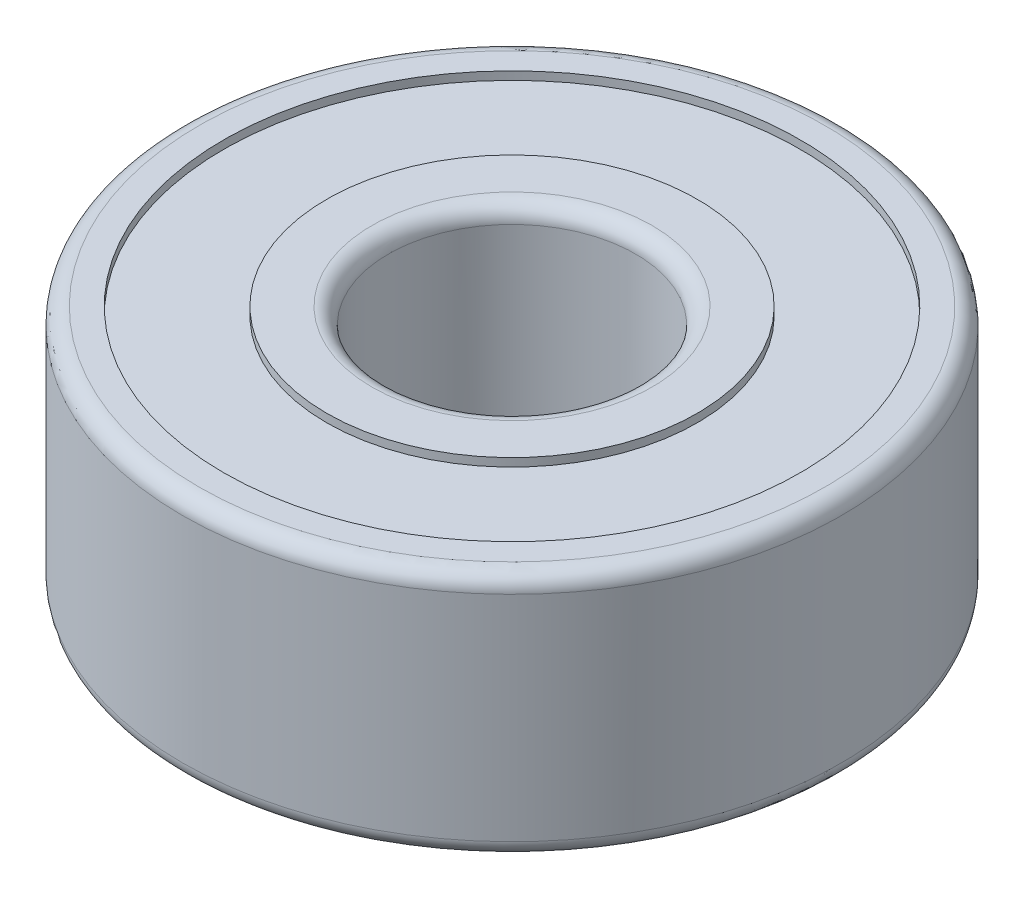
SolidWorks part; units mm, degrees
material "Plain Carbon Steel"
ref_plane "Front Plane" through (0, 0, 0) normal (0, 0, 1) x (1, 0, 0)
ref_plane "Top Plane" through (0, 0, 0) normal (0, 1, 0) x (1, 0, 0)
ref_plane "Right Plane" through (0, 0, 0) normal (1, 0, 0) x (0, 0, -1)
sketch "Sketch1" plane through (0, 0, 0) normal (1, 0, 0) x (0, 0, -1)
  line L0 (-4, 1.5) -> (-3.5, 1.5)
  line L1 (-3.5, 1.5) -> (-3.5, 1.4)
  line L2 (-3.5, 1.4) -> (-2.25, 1.4)
  line L3 (-2.25, 1.4) -> (-2.25, 1.5)
  line L4 (-2.25, 1.5) -> (-1.5, 1.5)
  line L5 (-1.5, 1.5) -> (-1.5, 0)
  line L6 (-1.5, 0) -> (-4, 0)
  line L7 (-4, 0) -> (-4, 1.5)
  line L8 (0, 17.3077) -> (0, -10.2308) construction
  point P11 (-2.75, 0)
  point P12 (-0.7832, 2.4512)
  point P13 (0.4642, 3.2135)
  point P14 (-3.0355, 1.5)
  point P15 (-2.0826, 1.4983)
  dimension "D1" = 3
  dimension "D2" = 8
  dimension "D3" = 1.5
  dimension "D4" = 0.75
  dimension "D5" = 0.5
  dimension "D6" = 0.1
revolve "Revolve1" add sketch "Sketch1" angle 360 about L8
fillet "Fillet1" radius 0.2 2 edges at (0, 1.5, 1.5) (0, 1.5, 4)
mirror "Mirror1" about plane through (0, 0, 0) normal (0, 1, 0) of "Fillet1", "Revolve1"
